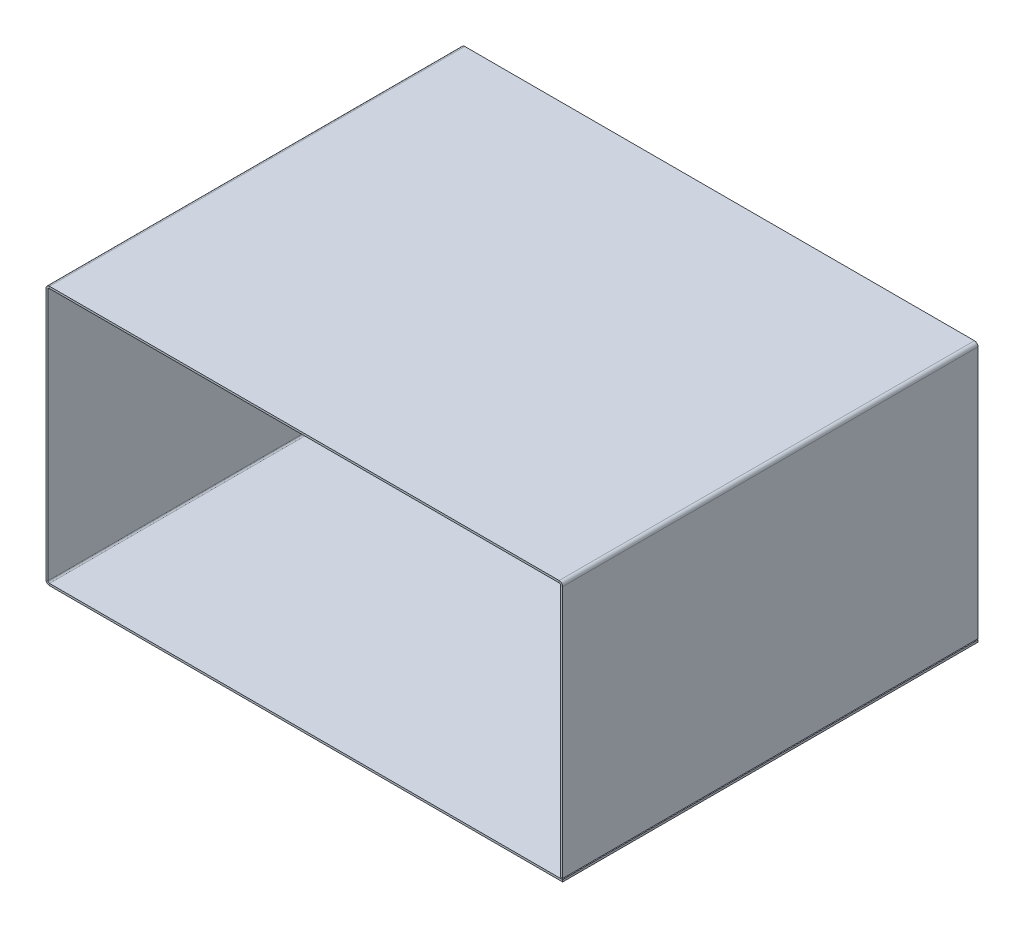
SolidWorks part; units mm, degrees
note: The reader was unsure of these and kept them because the rebuilt part matched: flange length of "Edge-Flange1", "Edge-Flange2", "Edge-Flange3".
ref_plane "Front Plane" through (0, 0, 0) normal (0, 0, 1) x (1, 0, 0)
ref_plane "Top Plane" through (0, 0, 0) normal (0, 1, 0) x (1, 0, 0)
ref_plane "Right Plane" through (0, 0, 0) normal (1, 0, 0) x (0, 0, -1)
sketch "Sketch1" plane through (0, 0, 0) normal (0, 1, 0) x (1, 0, 0)
  line L1 (-127.5, 102.5) -> (127.5, 102.5)
  line L2 (-127.5, 102.5) -> (-127.5, -102.5)
  line L3 (-127.5, -102.5) -> (127.5, -102.5)
  line L4 (127.5, 102.5) -> (127.5, -102.5)
  line L5 (0, -102.5) -> (0, 102.5) construction
  line L6 (-127.5, 0) -> (127.5, 0) construction
  point P0 (0, 0)
  dimension "D1" = 205
  dimension "D2" = 255
base flange "Base-Flange1" sketch "Sketch1" thickness 1 reverse thickness direction no parameters "D1"=0.7366
edge flange "Edge-Flange1" sketch "Sketch8" flange angle 90 flange length 128 flange position material inside bend radius 0.7366 thickness 1 relief rectangular parameters "D6"=10
sketch "Sketch8" plane through (-127.5, 0, 0) normal (-1, 0, 0) x (0, 0, 1)
  line L2 (-102.5, 0) -> (-102.5, 127)
  line L3 (-102.5, 127) -> (102.5, 127)
  line L4 (102.5, 127) -> (102.5, 0)
  line L7 (-102.5, 0) -> (102.5, 0) construction
  line L8 (-102.5, 0) -> (102.5, 0)
bend "EdgeBend1" bend radius 0.7366 bend angle 90 parameters "D5"=1
edge flange "Edge-Flange2" sketch "Sketch11" flange angle 90 flange length 255 flange position material inside bend radius 0.7366 thickness 1 relief rectangular parameters "D6"=10
sketch "Sketch11" plane through (-126.5, 127, 0) normal (0, 1, 0) x (0, 0, 1)
  line L2 (-102.5, 0) -> (-102.5, 254)
  line L3 (-102.5, 254) -> (102.5, 254)
  line L4 (102.5, 254) -> (102.5, 0)
  line L7 (102.5, 0) -> (-102.5, 0) construction
  line L8 (102.5, 0) -> (-102.5, 0)
bend "EdgeBend2" bend radius 0.7366 bend angle 90 parameters "D5"=2
edge flange "Edge-Flange3" sketch "Sketch14" flange angle 90 flange length 126.5 flange position material inside bend radius 0.7366 thickness 1 relief rectangular parameters "D6"=10
sketch "Sketch14" plane through (127.5, 126, 0) normal (-1, 0, 0) x (0, 0, -1)
  line L2 (-102.5, 0) -> (-102.5, 125.5)
  line L3 (-102.5, 125.5) -> (102.5, 125.5)
  line L4 (102.5, 125.5) -> (102.5, 0)
  line L5 (102.5, 0) -> (-102.5, 0) construction
  line L6 (102.5, 0) -> (-102.5, 0)
bend "EdgeBend3" bend radius 0.7366 bend angle 90 parameters "D5"=3
sketch "Bend-Lines1" [suppressed] plane through (0, 0, 0) normal (0, 1, 0) x (1, 0, 0)
sketch "Bounding-Box1" [suppressed] plane through (0, 0, 0) normal (0, 1, 0) x (1, 0, 0)
sheet metal parameters "Sheet-Metal1" thickness 1 parameters "D1"=0.7366
flat pattern "Flat-Pattern1" [suppressed]
sketch "Bend-Lines2" plane through (0, 0, 0) normal (0, 1, 0) x (1, 0, 0)
sketch3d "Bounding-Box2" [suppressed]
  line L0 (-127.5, -102.5, 0) -> (127.5, -102.5, 0) construction
  line L1 (-127.5, 102.5, 0) -> (127.5, 102.5, 0) construction
  line L2 (-127.5, -102.5, 0) -> (-127.5, 102.5, 0) construction
  line L3 (127.5, -102.5, 0) -> (127.5, 102.5, 0) construction
sheet metal parameters "Sheet-Metal2" thickness 1 parameters "D1"=0.7366
flat pattern "Flat-Pattern1"
sketch "Bend-Lines2" plane through (0, 0, 0) normal (0, 1, 0) x (1, 0, 0)
  line L0 (-126.7346, 102.5) -> (-126.7346, -102.5) construction
  line L1 (-126.7346, 102.5) -> (-126.7346, -102.5) construction
sketch3d "Bounding-Box2" [suppressed]
  line L0 (127.5, -102.5, 0) -> (-253.9692, -102.5, 0) construction
  line L1 (127.5, 102.5, 0) -> (-253.9692, 102.5, 0) construction
  line L2 (127.5, -102.5, 0) -> (127.5, 102.5, 0) construction
  line L3 (-253.9692, -102.5, 0) -> (-253.9692, 102.5, 0) construction
bend of the flat pattern "Flatten-<EdgeBend1>1"
sheet metal parameters "Sheet-Metal3" thickness 1 parameters "D1"=0.7366
flat pattern "Flat-Pattern1"
sketch "Bend-Lines2" plane through (0, 0, 0) normal (0, 1, 0) x (1, 0, 0)
  line L0 (-126.7346, 102.5) -> (-126.7346, -102.5) construction
  line L1 (-126.7346, 102.5) -> (-126.7346, -102.5) construction
  line L2 (-253.2039, 102.5) -> (-253.2039, -102.5) construction
  line L3 (-253.2039, 102.5) -> (-253.2039, -102.5) construction
sketch3d "Bounding-Box2" [suppressed]
  line L0 (127.5, -102.5, 0) -> (-507.4385, -102.5, 0) construction
  line L1 (127.5, 102.5, 0) -> (-507.4385, 102.5, 0) construction
  line L2 (127.5, -102.5, 0) -> (127.5, 102.5, 0) construction
  line L3 (-507.4385, -102.5, 0) -> (-507.4385, 102.5, 0) construction
bend of the flat pattern "Flatten-<EdgeBend1>1"
bend of the flat pattern "Flatten-<EdgeBend2>1"
sheet metal parameters "Sheet-Metal4" thickness 1 parameters "D1"=0.7366
flat pattern "Flat-Pattern1"
sketch "Bend-Lines2" plane through (0, 0, 0) normal (0, 1, 0) x (1, 0, 0)
  line L0 (-126.7346, 102.5) -> (-126.7346, -102.5) construction
  line L1 (-126.7346, 102.5) -> (-126.7346, -102.5) construction
  line L2 (-253.2039, 102.5) -> (-253.2039, -102.5) construction
  line L3 (-253.2039, 102.5) -> (-253.2039, -102.5) construction
  line L4 (-506.6731, 102.5) -> (-506.6731, -102.5) construction
  line L5 (-506.6731, 102.5) -> (-506.6731, -102.5) construction
sketch3d "Bounding-Box2" [suppressed]
  line L0 (127.5, -102.5, 0) -> (-632.4077, -102.5, 0) construction
  line L1 (127.5, 102.5, 0) -> (-632.4077, 102.5, 0) construction
  line L2 (127.5, -102.5, 0) -> (127.5, 102.5, 0) construction
  line L3 (-632.4077, -102.5, 0) -> (-632.4077, 102.5, 0) construction
bend of the flat pattern "Flatten-<EdgeBend1>1"
bend of the flat pattern "Flatten-<EdgeBend2>1"
bend of the flat pattern "Flatten-<EdgeBend3>1"
